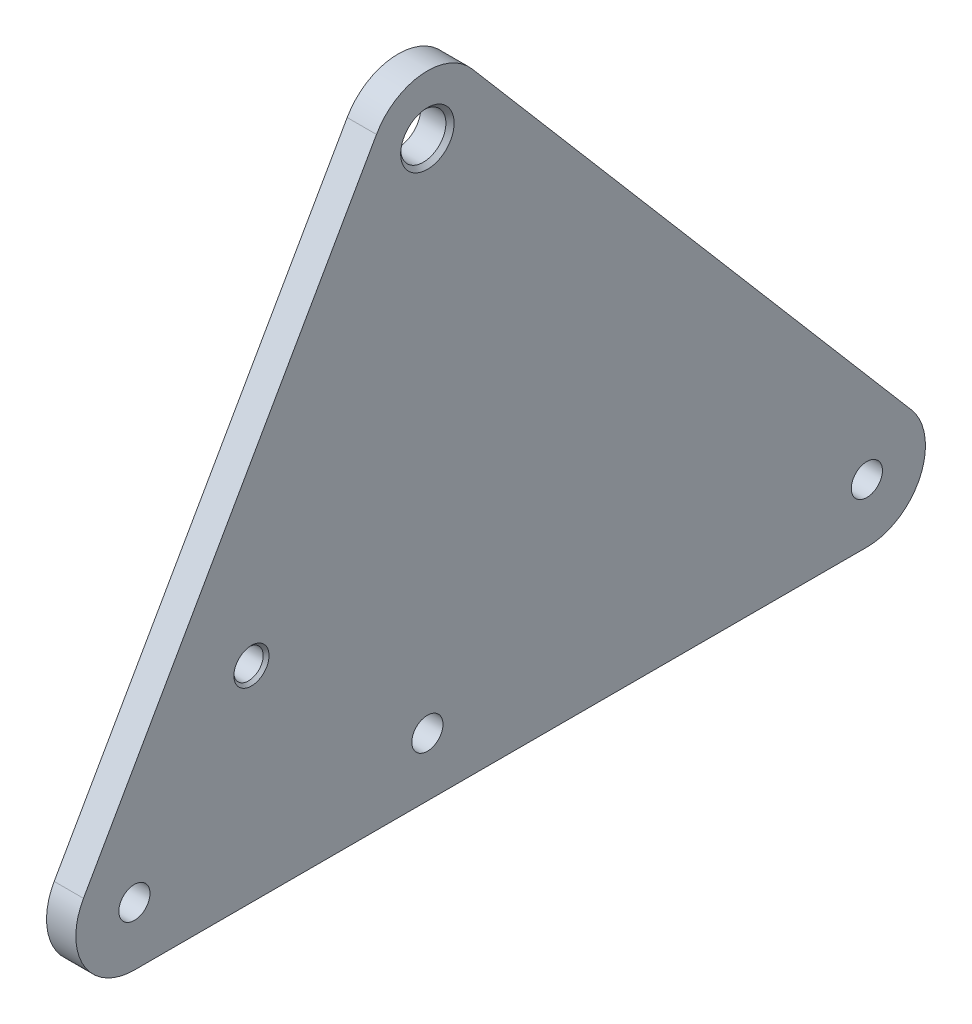
SolidWorks part; units mm, degrees
material "1060 Alloy"
ref_plane "Front Plane" through (0, 0, 0) normal (0, 0, 1) x (1, 0, 0)
ref_plane "Top Plane" through (0, 0, 0) normal (0, 1, 0) x (1, 0, 0)
ref_plane "Right Plane" through (0, 0, 0) normal (1, 0, 0) x (0, 0, -1)
sketch "Sketch1" plane through (0, 0, 0) normal (1, 0, 0) x (0, 0, -1)
  line L0 (-74.539, -105.3537) -> (-11.039, 6.2793)
  line L1 (9.6612, 8.2433) -> (104.9112, -103.3897)
  line L2 (-63.5, -124.333) -> (95.25, -124.333)
  arc A0 (9.6612, 8.2433) -> (-11.039, 6.2793) centre (0, 0) ccw
  arc A1 (95.25, -124.333) -> (104.9112, -103.3897) centre (95.25, -111.633) ccw
  arc A2 (-74.539, -105.3537) -> (-63.5, -124.333) centre (-63.5, -111.633) ccw
  dimension "D1" = 158.75
  dimension "D2" = 111.633
  dimension "D4" = 25.4
  dimension "D5" = 95.25
extrude "Boss-Extrude1" add sketch "Sketch1" along normal blind 6.35 contours L1 A1 L2 A2 L0 A0
sketch "Sketch2" plane through (6.35, 0, 0) normal (1, 0, 0) x (0, 0, -1)
  circle A0 centre (-63.5, -111.633) radius 3.3782
  circle A1 centre (0, -111.633) radius 3.3782
  circle A2 centre (95.25, -111.633) radius 3.3782
  arc A3 (-74.539, -105.3537) -> (-63.5, -124.333) centre (-63.5, -111.633) ccw construction
  arc A4 (95.25, -124.333) -> (104.9112, -103.3897) centre (95.25, -111.633) ccw construction
  dimension "D2" = 0
  dimension "D3" = 0
  dimension "D4" = 63.5
  dimension "D5" = 6.7564
extrude "Cut-Extrude1" cut sketch "Sketch2" against normal up to next
hole_wizard "3/8 Clearance Hole1" positions "Sketch3" profile "Sketch4" hole size "3/8" standard "ANSI Inch" end condition through all
sketch "Sketch3" plane through (6.35, 0, 0) normal (1, 0, 0) x (0, 0, -1)
  point P0 (0, 0)
sketch "Sketch4" plane through (6.35, 0, 0) normal (0, 1, 0) x (0, 0, -1)
  line L0 (0, 0) -> (0, 6.35)
  line L1 (0, 6.35) -> (4.9022, 6.35)
  line L2 (4.9022, 6.35) -> (4.9022, 0.8915)
  line L3 (4.9022, 0.8915) -> (5.7937, 0)
  line L5 (5.7937, 0) -> (0, 0)
  line L6 (-4.9022, 0.8915) -> (-5.7937, 0) construction
  line L11 (0, -6.35) -> (0, 107.95) construction
  dimension "Thru Hole Dia." = 9.8044
  dimension "Thru Hole Depth" = 6.35
  dimension "Near C'Sink Dia." = 11.5875
  dimension "Near C'Sink Angle" = 90
hole_wizard "1/4 (0.2500) Dowel Hole1" positions "Sketch5" profile "Sketch6" hole size "1/4" standard "ANSI Inch" end condition through all
sketch "Sketch5" plane through (6.35, 0, 0) normal (1, 0, 0) x (0, 0, -1)
  line L0 (-63.5, -124.333) -> (95.25, -124.333) construction
  line L1 (-74.539, -105.3537) -> (-11.039, 6.2793) construction
  point P0 (-38.1343, -79.883)
  dimension "D1" = 44.45
  dimension "D2" = 19.05
sketch "Sketch6" plane through (6.35, -79.883, 38.1343) normal (0, 1, 0) x (0, 0, -1)
  line L0 (0, 0) -> (0, 6.35)
  line L1 (0, 6.35) -> (3.175, 6.35)
  line L2 (3.175, 6.35) -> (3.175, 0.635)
  line L3 (3.175, 0.635) -> (3.81, 0)
  line L5 (3.81, 0) -> (0, 0)
  line L6 (-3.175, 0.635) -> (-3.81, 0) construction
  line L11 (0, -6.35) -> (0, 107.95) construction
  dimension "Thru Hole Dia." = 6.35
  dimension "Thru Hole Depth" = 6.35
  dimension "Near C'Sink Dia." = 7.62
  dimension "Near C'Sink Angle" = 90
